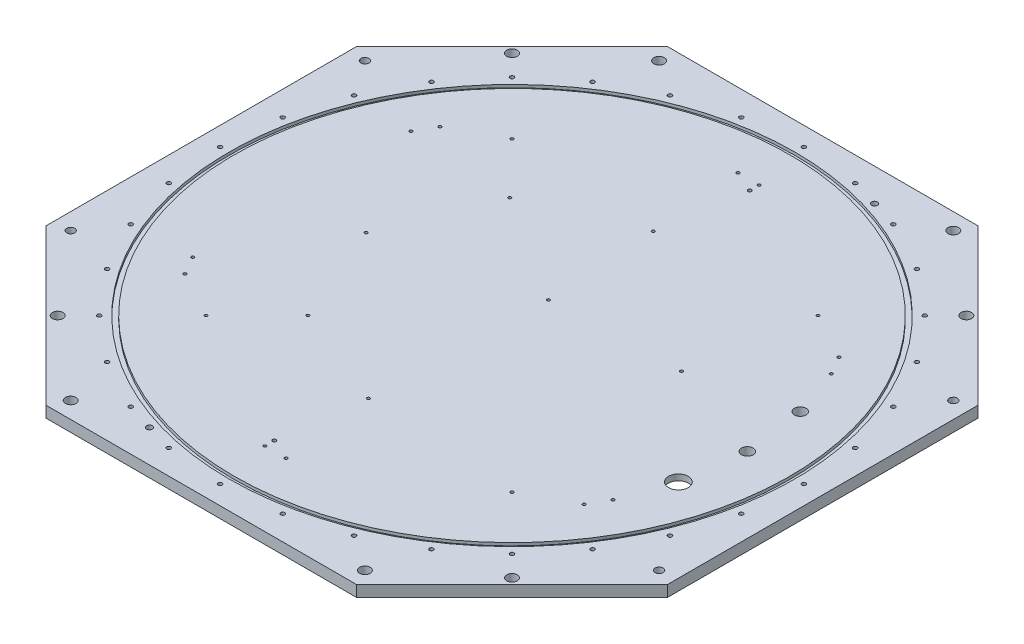
SolidWorks part; units mm, degrees
material "AISI 304"
ref_plane "Front" through (0, 0, 0) normal (0, 0, 1) x (1, 0, 0)
ref_plane "Top" through (0, 0, 0) normal (0, 1, 0) x (1, 0, 0)
ref_plane "Right" through (0, 0, 0) normal (1, 0, 0) x (0, 0, -1)
ref_axis "Axis1" through (0, -5.2388, 0) along (0, 1, 0)
sketch "Sketch1" plane through (0, 0, 0) normal (0, 1, 0) x (1, 0, 0)
  line L0 (-131.9798, 264) -> (131.9798, 264)
  line L1 (131.9798, 264) -> (264, 131.9798)
  line L2 (264, 131.9798) -> (264, -131.9798)
  line L3 (264, 0) -> (0, 0) construction
  line L4 (0, 0) -> (0, 264) construction
  line L5 (131.9798, -264) -> (264, -131.9798)
  line L6 (-131.9798, -264) -> (131.9798, -264)
  line L7 (-131.9798, -264) -> (-264, -131.9798)
  line L8 (-264, 131.9798) -> (-264, -131.9798)
  line L9 (-131.9798, 264) -> (-264, 131.9798)
  point P12 (0, -264)
  point P21 (0, 0)
  dimension "D1" = 528
  dimension "D2" = 280
extrude "Base Plate Profile" add sketch "Sketch1" along normal mid plane 9.525
hole_wizard "M3 Clearance Hole - For Cylinder" positions "Sketch2" profile "Sketch3" hole size "M3" standard "ANSI Metric" end condition up to next
sketch "Sketch2" plane through (0, 4.7625, 0) normal (0, 1, 0) x (1, 0, 0)
  line L0 (-248, 0) -> (248, 0) construction
  point P0 (248, 0)
  point P6 (243.2347, -48.3824)
  point P7 (229.1221, -94.9055)
  point P8 (206.2045, -137.7814)
  point P9 (175.3625, -175.3625)
  point P10 (137.7814, -206.2045)
  point P11 (94.9055, -229.1221)
  point P12 (48.3824, -243.2347)
  point P13 (0, -248)
  point P14 (-48.3824, -243.2347)
  point P15 (-94.9055, -229.1221)
  point P16 (-137.7814, -206.2045)
  point P17 (-175.3625, -175.3625)
  point P18 (-206.2045, -137.7814)
  point P19 (-229.1221, -94.9055)
  point P20 (-243.2347, -48.3824)
  point P21 (-248, 0)
  point P22 (-243.2347, 48.3824)
  point P23 (-229.1221, 94.9055)
  point P24 (-206.2045, 137.7814)
  point P25 (-175.3625, 175.3625)
  point P26 (-137.7814, 206.2045)
  point P27 (-94.9055, 229.1221)
  point P28 (-48.3824, 243.2347)
  point P29 (0, 248)
  point P30 (48.3824, 243.2347)
  point P31 (94.9055, 229.1221)
  point P32 (137.7814, 206.2045)
  point P33 (175.3625, 175.3625)
  point P34 (206.2045, 137.7814)
  point P35 (229.1221, 94.9055)
  point P36 (243.2347, 48.3824)
  dimension "D2" = 496
  dimension "D1" = 32
sketch "Sketch3" plane through (248, 4.7625, 0) normal (1, 0, 0) x (0, 0, 1)
  line L0 (0, 0) -> (0, 9.525)
  line L1 (0, 9.525) -> (1.7, 9.525)
  line L2 (1.7, 9.525) -> (1.7, 0)
  line L5 (1.7, 0) -> (0, 0)
  line L11 (0, -6.35) -> (0, 107.95) construction
  dimension "Thru Hole Dia." = 3.4
  dimension "Thru Hole Depth" = 9.525
hole_wizard "M3x0.5 Tapped Hole - For Support Pillars" positions "Sketch10" profile "Sketch11" tap size "M3x0.5" standard "ANSI Metric"
sketch "Sketch10" plane through (0, 4.7625, 0) normal (0, 1, 0) x (1, 0, 0)
  line L0 (-9, 201) -> (0, 201) construction
  line L1 (0, 201) -> (9, 201) construction
  line L6 (0, 0) -> (0, 201) construction
  line L7 (-9, -201) -> (9, -201) construction
  line L9 (0, -201) -> (0, 0) construction
  point P0 (-9, 201)
  point P2 (9, 201)
  point P39 (169.5711, 108.2942)
  point P40 (178.5711, 92.7058)
  point P41 (178.5711, -92.7058)
  point P42 (169.5711, -108.2942)
  point P43 (9, -201)
  point P44 (-9, -201)
  point P45 (-169.5711, -108.2942)
  point P46 (-178.5711, -92.7058)
  point P47 (-178.5711, 92.7058)
  point P48 (-169.5711, 108.2942)
  dimension "D1" = 18
  dimension "D2" = 6
  dimension "D3" = 201
sketch "Sketch11" plane through (-9, 4.7625, -201) normal (1, 0, 0) x (0, 0, 1)
  line L0 (0, 0) -> (0, 8.2511)
  line L1 (0, 8.2511) -> (1.25, 7.5)
  line L2 (1.25, 7.5) -> (1.25, 0)
  line L5 (1.25, 0) -> (0, 0)
  line L10 (0, 8.2511) -> (-1.25, 7.5) construction
  line L11 (0, -6.35) -> (0, 107.95) construction
  dimension "Tap Drill Dia." = 2.5
  dimension "Tap Drill Depth" = 7.5
  dimension "Drill Angle" = 118
cosmetic thread "Hole Thread1" parameters "D1"=6, "D2"=3
cosmetic thread "Hole Thread2" parameters "D1"=6, "D2"=3
cosmetic thread "Hole Thread3" parameters "D1"=6, "D2"=3
cosmetic thread "Hole Thread4" parameters "D1"=6, "D2"=3
cosmetic thread "Hole Thread5" parameters "D1"=6, "D2"=3
cosmetic thread "Hole Thread6" parameters "D1"=6, "D2"=3
cosmetic thread "Hole Thread7" parameters "D1"=6, "D2"=3
cosmetic thread "Hole Thread8" parameters "D1"=6, "D2"=3
cosmetic thread "Hole Thread9" parameters "D1"=6, "D2"=3
cosmetic thread "Hole Thread10" parameters "D1"=6, "D2"=3
cosmetic thread "Hole Thread11" parameters "D1"=6, "D2"=3
cosmetic thread "Hole Thread12" parameters "D1"=6, "D2"=3
hole_wizard "Ø3.0mm Dowel Hole - For Support Pillars" positions "Sketch12" profile "Sketch13" hole size "Ø3.0" standard "ANSI Metric"
sketch "Sketch12" plane through (0, 4.7625, 0) normal (0, 1, 0) x (1, 0, 0)
  line L1 (9, 193) -> (9, 201) construction
  line L3 (-9, -201) -> (-9, -193) construction
  point P0 (9, 193)
  point P2 (-9, -193)
  dimension "D1" = 8
sketch "Sketch13" plane through (9, 4.7625, -193) normal (1, 0, 0) x (0, 0, 1)
  line L0 (0, 0) -> (0, 6.9013)
  line L1 (0, 6.9013) -> (1.5, 6)
  line L2 (1.5, 6) -> (1.5, 0)
  line L5 (1.5, 0) -> (0, 0)
  line L10 (0, 6.9013) -> (-1.5, 6) construction
  line L11 (0, -6.35) -> (0, 107.95) construction
  dimension "Hole Dia." = 3
  dimension "Hole Depth" = 6
  dimension "Drill Angle" = 118
hole_wizard "M3x0.5 Tapped Hole - For PCB Standoffs" positions "Sketch14" profile "Sketch15" tap size "M3x0.5" standard "ANSI Metric"
sketch "Sketch14" plane through (0, 4.7625, 0) normal (0, 1, 0) x (1, 0, 0)
  line L13 (-150, -150) -> (150, -150) construction
  line L14 (-150, -150) -> (-150, 150) construction
  line L15 (-150, 150) -> (150, 150) construction
  line L16 (150, -150) -> (150, 150) construction
  line L17 (-150, -150) -> (150, 150) construction
  line L18 (-150, 150) -> (150, -150) construction
  point P133 (-130, -130)
  point P136 (130, -130)
  point P138 (130, 130)
  point P140 (-130, 130)
  point P143 (-86.8, -86.7)
  point P145 (0, -122)
  point P149 (-123, -1)
  point P152 (-87.7, 85.8)
  point P154 (4, 27)
  point P157 (-2, 122)
  point P159 (113, 31)
  dimension "D1" = 300
  dimension "D3" = 63.2
  dimension "D4" = 63.3
  dimension "D5" = 28
  dimension "D2" = 20
  dimension "D6" = 27
  dimension "D7" = 149
  dimension "D8" = 235.8
  dimension "D9" = 62.3
  dimension "D10" = 154
  dimension "D11" = 177
  dimension "D12" = 148
  dimension "D13" = 272
  dimension "D14" = 181
  dimension "D15" = 263
sketch "Sketch15" plane through (113, 4.7625, -31) normal (1, 0, 0) x (0, 0, 1)
  line L0 (0, 0) -> (0, 7.2511)
  line L1 (0, 7.2511) -> (1.25, 6.5)
  line L2 (1.25, 6.5) -> (1.25, 0)
  line L5 (1.25, 0) -> (0, 0)
  line L10 (0, 7.2511) -> (-1.25, 6.5) construction
  line L11 (0, -6.35) -> (0, 107.95) construction
  dimension "Tap Drill Dia." = 2.5
  dimension "Tap Drill Depth" = 6.5
  dimension "Drill Angle" = 118
cosmetic thread "Hole Thread13" parameters "D1"=5, "D2"=3
cosmetic thread "Hole Thread14" parameters "D1"=5, "D2"=3
cosmetic thread "Hole Thread15" parameters "D1"=5, "D2"=3
cosmetic thread "Hole Thread16" parameters "D1"=5, "D2"=3
cosmetic thread "Hole Thread17" parameters "D1"=5, "D2"=3
cosmetic thread "Hole Thread18" parameters "D1"=5, "D2"=3
cosmetic thread "Hole Thread19" parameters "D1"=5, "D2"=3
cosmetic thread "Hole Thread20" parameters "D1"=5, "D2"=3
cosmetic thread "Hole Thread21" parameters "D1"=5, "D2"=3
cosmetic thread "Hole Thread22" parameters "D1"=5, "D2"=3
cosmetic thread "Hole Thread23" parameters "D1"=5, "D2"=3
sketch "PCB Size Outline" plane through (0, -4.7625, 0) normal (0, -1, 0) x (1, 0, 0)
  line L1 (-150, -150) -> (150, -150)
  line L2 (-150, -150) -> (-150, 150)
  line L3 (-150, 150) -> (150, 150)
  line L4 (150, -150) -> (150, 150)
  line L5 (-150, -150) -> (150, 150) construction
  line L6 (-150, 150) -> (150, -150) construction
  point P0 (0, 0)
  dimension "D1" = 300
hole_wizard "M8 Clearance Hole - For Lifting / Alignment" positions "Sketch16" profile "Sketch17" hole size "M8" standard "ANSI Metric" end condition up to next
sketch "Sketch16" plane through (0, 4.7625, 0) normal (0, 1, 0) x (1, 0, 0)
  line L0 (-193.0402, 193.0402) -> (-193.0402, -193.0402) construction
  line L1 (-193.0402, -193.0402) -> (193.0402, -193.0402) construction
  line L2 (193.0402, -193.0402) -> (193.0402, 193.0402) construction
  line L3 (193.0402, 193.0402) -> (-193.0402, 193.0402) construction
  line L5 (-193.0402, 193.0402) -> (193.0402, -193.0402) construction
  point P0 (-193.0402, -193.0402)
  point P6 (-193.0402, 193.0402)
  point P7 (193.0402, 193.0402)
  point P8 (193.0402, -193.0402)
  dimension "D2" = 546
  dimension "D1" = 4
sketch "Sketch17" plane through (-193.0402, 4.7625, 193.0402) normal (1, 0, 0) x (0, 0, 1)
  line L0 (0, 0) -> (0, 9.525)
  line L1 (0, 9.525) -> (4.5, 9.525)
  line L2 (4.5, 9.525) -> (4.5, 0)
  line L5 (4.5, 0) -> (0, 0)
  line L11 (0, -6.35) -> (0, 107.95) construction
  dimension "Thru Hole Dia." = 9
  dimension "Thru Hole Depth" = 9.525
hole_wizard "M8x1.25 Tapped Hole -For Super Structure" positions "Sketch18" profile "Sketch19" tap size "M8x1.25" standard "ANSI Metric" end condition up to next
sketch "Sketch18" plane through (0, 4.7625, 0) normal (0, 1, 0) x (1, 0, 0)
  line L0 (-264, 0) -> (0, 0) construction
  line L1 (-264, 131.9798) -> (-264, -131.9798) construction
  line L2 (0, 0) -> (0, -264) construction
  line L3 (-131.9798, -264) -> (131.9798, -264) construction
  line L5 (0, 0) -> (-197.9899, -197.9899) construction
  line L6 (-264, -131.9798) -> (-131.9798, -264) construction
  point P22 (-250, -125)
  point P25 (-250, 125)
  point P27 (250, -125)
  point P28 (250, 125)
  dimension "D2" = 250
  dimension "D3" = 500
sketch "Sketch19" plane through (250, 4.7625, -125) normal (1, 0, 0) x (0, 0, 1)
  line L0 (0, 0) -> (0, 9.525)
  line L1 (0, 9.525) -> (3.4, 9.525)
  line L2 (3.4, 9.525) -> (3.4, 0)
  line L5 (3.4, 0) -> (0, 0)
  line L11 (0, -6.35) -> (0, 107.95) construction
  dimension "Thru Tap Drill Dia." = 6.8
  dimension "Thru Tap Drill Depth" = 9.525
cosmetic thread "Hole Thread34" parameters "D2"=8
cosmetic thread "Hole Thread35" parameters "D2"=8
cosmetic thread "Hole Thread37" parameters "D2"=8
cosmetic thread "Hole Thread39" parameters "D2"=8
hole_wizard "7/16-20 Tapped Hole - For Penetrator" positions "Sketch25" profile "Sketch26" tap size "7/16-20" standard "ANSI Inch" end condition up to next
sketch "Sketch25" plane through (0, -4.7625, 0) normal (0, -1, 0) x (-1, 0, 0)
  point P0 (-200, 0)
  dimension "D1" = 200
cosmetic thread "Hole Thread32" parameters "D2"=11.1125
sketch "Sketch26" plane through (200, -4.7625, 0) normal (1, 0, 0) x (0, 0, -1)
  line L0 (0, 0) -> (0, 9.525)
  line L1 (0, 9.525) -> (4.9606, 9.525)
  line L2 (4.9606, 9.525) -> (4.9606, 0)
  line L5 (4.9606, 0) -> (0, 0)
  line L11 (0, -6.35) -> (0, 107.95) construction
  dimension "Thru Tap Drill Dia." = 9.9212
  dimension "Thru Tap Drill Depth" = 9.525
sketch "Sketch28" plane through (0, 4.7625, 0) normal (0, 1, 0) x (1, 0, 0)
  line L0 (-150, -150) -> (150, 150) construction
  circle A0 centre (0, 0) radius 240.5
  circle A1 centre (0, 0) radius 236.3344
  dimension "D1" = 481
  dimension "D2" = 4.1656
extrude "O-ring Groove" cut sketch "Sketch28" against normal blind 2.413
sketch "Sketch_thickness" [suppressed] plane through (0, 0, 0) normal (1, 0, 0) x (0, 0, -1)
  line L0 (-88.2215, 4.7625) -> (-88.2215, -0.2425)
  line L1 (-131.9798, 4.7625) -> (131.9798, 4.7625) construction
  line L2 (-88.2215, -0.2425) -> (-88.2215, -4.7625)
  line L3 (-150, -4.7625) -> (150, -4.7625) construction
  dimension "D1" = 5.005
  dimension "D2" = 4.52
pattern_circular "CirPattern_extraCables" count 2 every 15 about axis through (0, -5.2388, 0) along (0, 1, 0) of "7/16-20 Tapped Hole - For Penetrator"
hole_wizard "5/8 Clearance Hole1" positions "Sketch32" profile "Sketch33" hole size "5/8" standard "ANSI Inch" end condition up to next
sketch "Sketch32" plane through (0, 4.7625, 0) normal (0, 1, 0) x (1, 0, 0)
  line L0 (0, 0) -> (193.1852, -51.7638) construction
  line L2 (0, 0) -> (200, 0) construction
  point P0 (193.1852, -51.7638)
  dimension "D1" = 200
  dimension "D2" = 15
sketch "Sketch33" plane through (193.1852, 4.7625, 51.7638) normal (1, 0, 0) x (0, 0, 1)
  line L0 (0, 0) -> (0, 9.525)
  line L1 (0, 9.525) -> (8.3337, 9.525)
  line L2 (8.3337, 9.525) -> (8.3337, 0)
  line L5 (8.3337, 0) -> (0, 0)
  line L11 (0, -6.35) -> (0, 107.95) construction
  dimension "Thru Hole Dia." = 16.6675
  dimension "Thru Hole Depth" = 9.525
sketch "Sketch35" plane through (0, -4.7625, 0) normal (0, -1, 0) x (1, 0, 0)
  circle A0 centre (193.1852, 51.7638) radius 18
  dimension "D1" = 36
extrude "Cut-Extrude1" cut sketch "Sketch35" against normal blind 4.5
hole_wizard "M8 Clearance Hole" positions "Sketch37" profile "Sketch39" hole size "M8" standard "ANSI Metric" end condition up to next
sketch "Sketch37" plane through (-28.1239, 4.7625, -48.0675) normal (0, 1, 0) x (1, 0, 0)
  line L0 (-235.8761, -48.0675) -> (28.1239, -48.0675) construction
  line L2 (28.1239, -48.0675) -> (28.1239, -312.0675) construction
  line L5 (28.1239, -48.0675) -> (-169.866, -246.0574) construction
  line L7 (-103.8559, -312.0675) -> (160.1037, -312.0675) construction
  line L8 (-235.8761, 83.9123) -> (-235.8761, -180.0473) construction
  line L9 (-235.8761, -180.0473) -> (-103.8559, -312.0675) construction
  point P0 (-96.8761, -298.0675)
  point P24 (-96.8761, 201.9325)
  point P26 (153.1239, -298.0675)
  point P29 (153.1239, 201.9325)
  dimension "D1" = 250
  dimension "D2" = 500
sketch "Sketch39" plane through (-125, 4.7625, 250) normal (1, 0, 0) x (0, 0, 1)
  line L0 (0, 0) -> (0, 9.525)
  line L1 (0, 9.525) -> (4.5, 9.525)
  line L2 (4.5, 9.525) -> (4.5, 0)
  line L5 (4.5, 0) -> (0, 0)
  line L11 (0, -6.35) -> (0, 107.95) construction
  dimension "Thru Hole Dia." = 9
  dimension "Thru Hole Depth" = 9.525
hole_wizard "Ø5.0mm Dowel Hole1" positions "Sketch42" profile "Sketch43" hole size "Ø5.0" standard "ANSI Metric"
sketch "Sketch42" plane through (0, 4.7625, 0) normal (0, 1, 0) x (1, 0, 0)
  point P0 (71.7003, 236.3643)
  point P3 (-71.7003, -236.3643)
sketch "Sketch43" plane through (71.7003, 4.7625, -236.3643) normal (1, 0, 0) x (0, 0, 1)
  line L0 (0, 0) -> (0, 6.5172)
  line L1 (0, 6.5172) -> (2.525, 5)
  line L2 (2.525, 5) -> (2.525, 0)
  line L5 (2.525, 0) -> (0, 0)
  line L10 (0, 6.5172) -> (-2.525, 5) construction
  line L11 (0, -6.35) -> (0, 107.95) construction
  dimension "Hole Dia." = 5.05
  dimension "Hole Depth" = 5
  dimension "Drill Angle" = 118
sketch "Sketch44" plane through (0, 4.7625, 0) normal (0, 1, 0) x (1, 0, 0)
  line L0 (178.5711, -92.7058) -> (169.5711, -108.2942) construction
sketch "Sketch45" plane through (0, 4.7625, 0) normal (0, 1, 0) x (1, 0, 0)
  line L0 (174.0711, -100.5) -> (188.6538, -108.9193) construction
  line L1 (178.5711, -92.7058) -> (169.5711, -108.2942) construction
